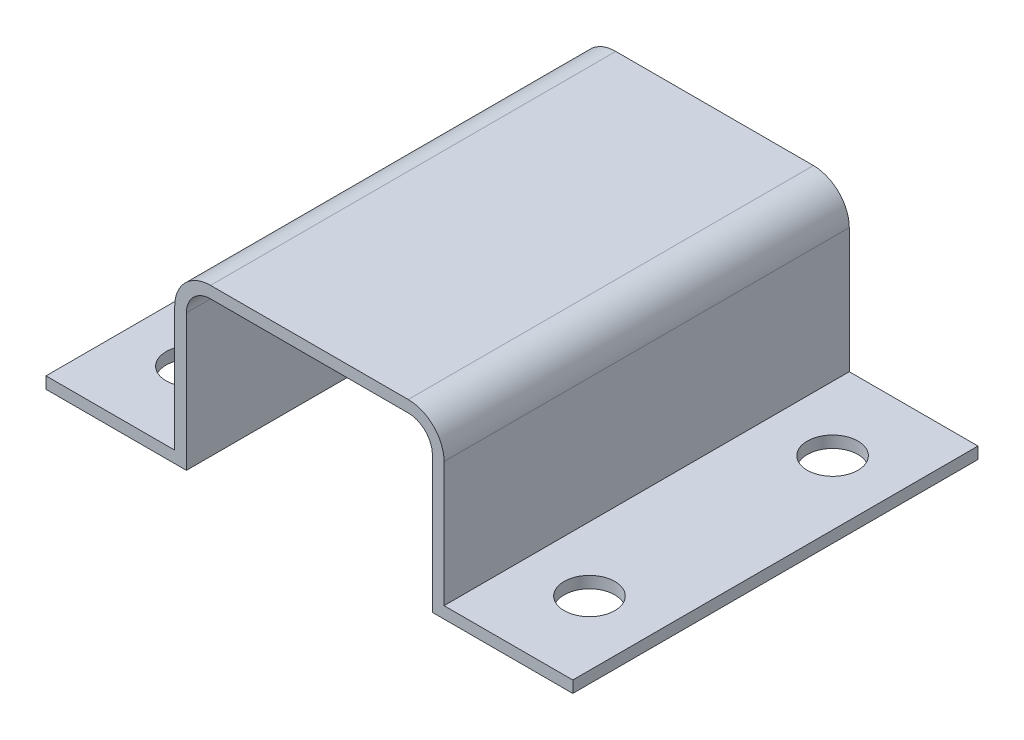
SolidWorks part; units mm, degrees
material "Plain Carbon Steel"
ref_plane "Front Plane" through (0, 0, 0) normal (0, 0, 1) x (1, 0, 0)
ref_plane "Top Plane" through (0, 0, 0) normal (0, 1, 0) x (1, 0, 0)
ref_plane "Right Plane" through (0, 0, 0) normal (1, 0, 0) x (0, 0, -1)
sketch "Sketch5" plane through (0, 0, 0) normal (0, 0, 1) x (1, 0, 0)
  line L0 (0, 0) -> (17.6022, 0)
  line L1 (17.6022, 0) -> (17.6022, 17.1109)
  line L2 (20.6292, 20.1378) -> (33.02, 20.1378)
  line L3 (0, 0) -> (0, 1.4643)
  line L4 (0, 1.4643) -> (16.1379, 1.4643)
  line L5 (16.1379, 1.4643) -> (16.1379, 17.1109)
  line L6 (20.6292, 21.6021) -> (33.02, 21.6021)
  line L7 (33.02, 21.6021) -> (33.02, 20.1378)
  line L8 (16.1379, 1.4643) -> (17.6022, 1.4643) construction
  arc A0 (17.6022, 17.1109) -> (20.6292, 20.1378) centre (20.6292, 17.1109) cw
  arc A1 (16.1379, 17.1109) -> (20.6292, 21.6021) centre (20.6292, 17.1109) cw
  dimension "D1" = 15.4178
  dimension "D2" = 17.6022
extrude "Boss-Extrude3" add sketch "Sketch5" along normal blind 50.8
mirror "Mirror6" about plane through (33.02, 21.6021, 50.8) normal (-1, 0, 0) of "Boss-Extrude3"
sketch "Sketch6" plane through (0, 1.4643, 0) normal (0, 1, 0) x (-1, 0, 0)
  line L0 (-8.0689, 50.8) -> (-8.0689, 40.64) construction
  line L1 (-16.1379, 50.8) -> (0, 50.8) construction
  line L2 (-8.0689, 0) -> (-8.0689, 10.16) construction
  line L3 (-16.1379, 0) -> (0, 0) construction
  line L4 (-57.9711, 50.8) -> (-57.9711, 40.64) construction
  line L5 (-49.9021, 50.8) -> (-66.04, 50.8) construction
  line L6 (-57.9711, 0) -> (-57.9711, 10.16) construction
  line L7 (-49.9021, 0) -> (-66.04, 0) construction
  circle A0 centre (-8.0689, 40.64) radius 3.175
  circle A1 centre (-8.0689, 10.16) radius 3.175
  circle A2 centre (-57.9711, 10.16) radius 3.175
  circle A3 centre (-57.9711, 40.64) radius 3.175
  dimension "D2" = 6.35
  dimension "D1" = 10.16
extrude "Cut-Extrude1" cut sketch "Sketch6" against normal up to next
